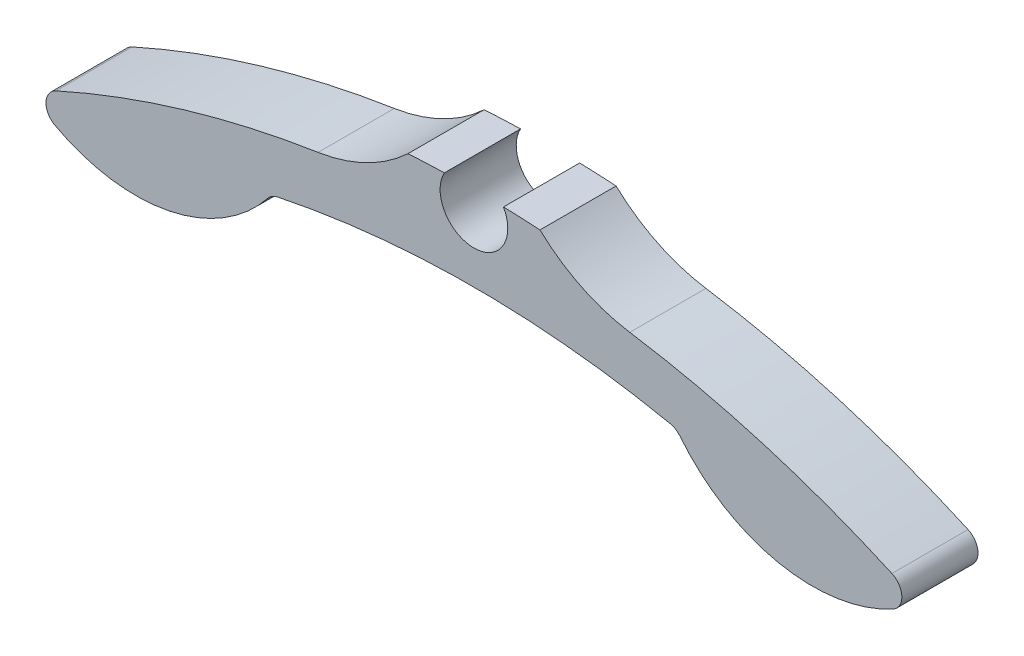
SolidWorks part; units mm, degrees
ref_plane "Front Plane" through (0, 0, 0) normal (0, 0, 1) x (1, 0, 0)
ref_plane "Top Plane" through (0, 0, 0) normal (0, 1, 0) x (1, 0, 0)
ref_plane "Right Plane" through (0, 0, 0) normal (1, 0, 0) x (0, 0, -1)
sketch "Sketch2" plane through (0, 0, 0) normal (0, 0, 1) x (1, 0, 0)
  line L0 (0, 0) -> (0, -61.1551) construction
  arc A0 (-1.746, 0.9755) -> (1.746, 0.9755) centre (0, 0) ccw
  circle A1 centre (0, -61.1551) radius 55 construction
  arc A2 (-27.8016, -5.5644) -> (-11.9693, -5.2673) centre (-20, 0.6915) ccw
  arc A3 (11.9693, -5.2673) -> (27.8016, -5.5644) centre (20, 0.6915) ccw
  arc A4 (11.9693, -5.2673) -> (-11.9693, -5.2673) centre (0, -61.1551) ccw
  arc A5 (27.8016, -5.5644) -> (1.746, 0.9755) centre (0, -61.1551) ccw
  arc A6 (-1.746, 0.9755) -> (-27.8016, -5.5644) centre (0, -61.1551) ccw
  point P1 (0, -6.1551)
  point P11 (0, -4)
  point P12 (0, -2)
  point P14 (0, 1)
  dimension "D1" = 4
  dimension "D2" = 110
  dimension "D3" = 20
  dimension "D4" = 40
  dimension "D5" = 2
  dimension "D6" = 1
  dimension "D7" = 2.1551
extrude "Boss-Extrude1" add sketch "Sketch2" along normal blind 4.5
sketch "Sketch3" plane through (0, 0, 4.5) normal (0, 0, 1) x (1, 0, 0)
  arc A0 (-3.8392, -1.1226) -> (-26.3159, -7.0616) centre (0, -61.1551) ccw
  arc A1 (-3.9026, 0.8774) -> (-27.8016, -5.5644) centre (0, -61.1551) ccw
  arc A2 (-3.9026, 0.8774) -> (-3.8392, -1.1226) centre (0, 0) ccw
  arc A13 (26.3159, -7.0616) -> (3.8392, -1.1226) centre (0, -61.1551) ccw
  arc A14 (-1.746, 0.9755) -> (-27.8016, -5.5644) centre (0, -61.1551) ccw construction
  arc A15 (27.8016, -5.5644) -> (3.9026, 0.8774) centre (0, -61.1551) ccw
  arc A16 (-27.8016, -5.5644) -> (-11.9693, -5.2673) centre (-20, 0.6915) ccw construction
  arc A17 (11.9693, -5.2673) -> (27.8016, -5.5644) centre (20, 0.6915) ccw construction
  arc A18 (-27.8016, -5.5644) -> (-26.3159, -7.0616) centre (-20, 0.6915) ccw
  arc A19 (26.3159, -7.0616) -> (27.8016, -5.5644) centre (20, 0.6915) ccw
  arc A20 (3.8392, -1.1226) -> (3.9026, 0.8774) centre (0, 0) ccw
  arc A21 (11.9693, -5.2673) -> (-11.9693, -5.2673) centre (0, -61.1551) ccw construction
  dimension "D1" = 2
extrude "Cut-Extrude1" cut sketch "Sketch3" against normal through all
fillet "Fillet1" radius 10 2 edges at (-3.8392, -1.1226, 2.25) (3.8392, -1.1226, 2.25)
fillet "Fillet2" radius 1 4 edges at (26.3159, -7.0616, 2.25) (11.9693, -5.2673, 2.25) (-11.9693, -5.2673, 2.25) (-26.3159, -7.0616, 2.25)
